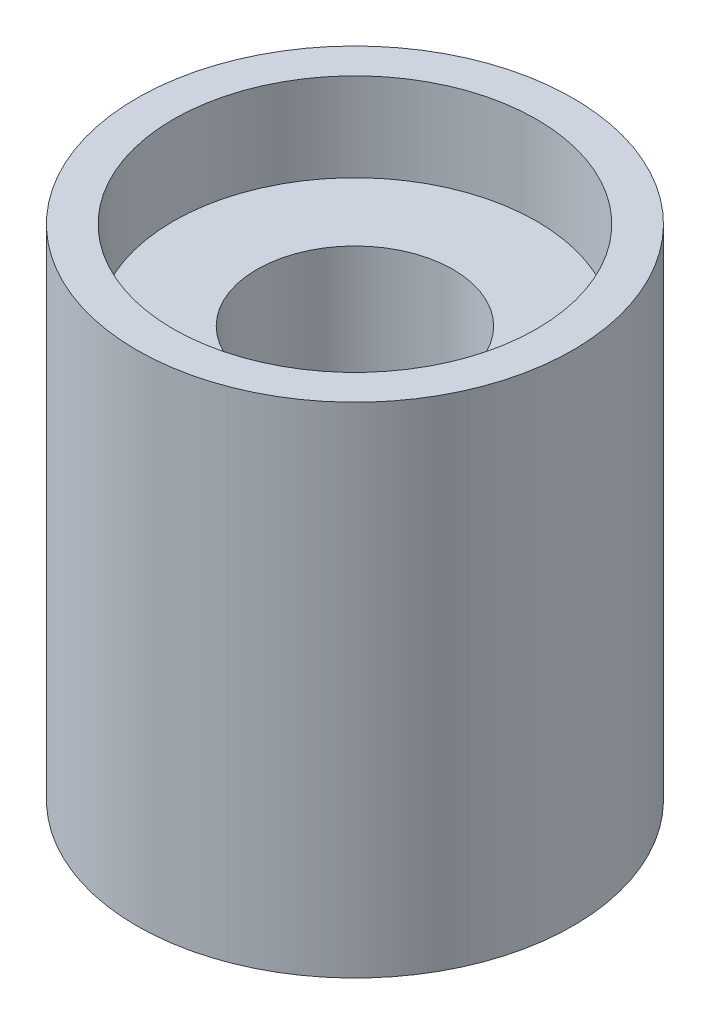
SolidWorks part; units mm, degrees
ref_plane "Front Plane" through (0, 0, 0) normal (0, 0, 1) x (1, 0, 0)
ref_plane "Top Plane" through (0, 0, 0) normal (0, 1, 0) x (1, 0, 0)
ref_plane "Right Plane" through (0, 0, 0) normal (1, 0, 0) x (0, 0, -1)
sketch "Sketch1" plane through (0, 0, 0) normal (0, 1, 0) x (1, 0, 0)
  circle A0 centre (0, 0) radius 22.225
  dimension "D1" = 44.45
extrude "Boss-Extrude1" add sketch "Sketch1" along normal blind 50.8
sketch "Sketch2" plane through (0, 50.8, 0) normal (0, 1, 0) x (1, 0, 0)
  circle A0 centre (0, 0) radius 18.5039
  dimension "D1" = 37.0078
extrude "Cut-Extrude1" cut sketch "Sketch2" against normal blind 8.9916
sketch "Sketch4" plane through (0, 0, 0) normal (0, -1, 0) x (1, 0, 0)
  circle A0 centre (0, 0) radius 18.5039
  dimension "D1" = 37.0078
extrude "Cut-Extrude2" cut sketch "Sketch4" against normal blind 8.9916
sketch "Sketch5" plane through (0, 8.9916, 0) normal (0, -1, 0) x (1, 0, 0)
  circle A0 centre (0, 0) radius 9.9949
  dimension "D1" = 19.9898
extrude "Cut-Extrude3" cut sketch "Sketch5" against normal through all
